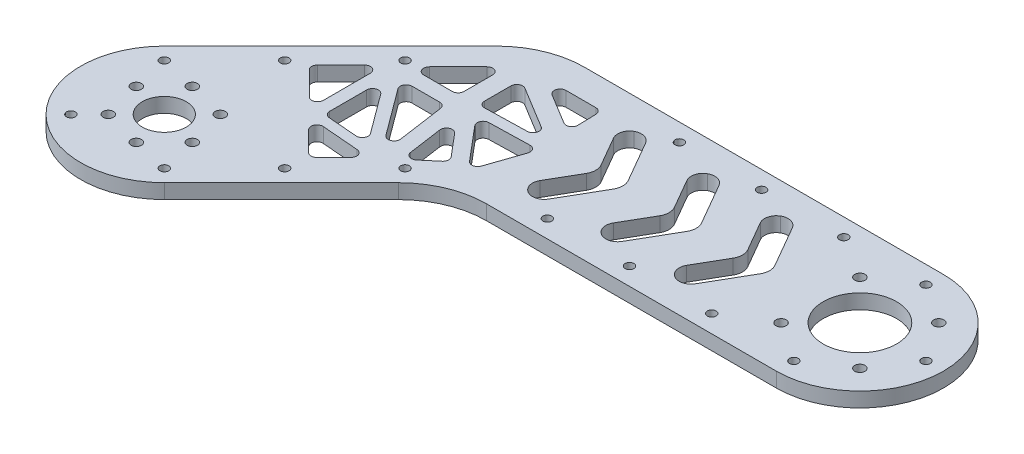
SolidWorks part; units mm, degrees
ref_plane "前视基准面" through (0, 0, 0) normal (0, 0, 1) x (1, 0, 0)
ref_plane "上视基准面" through (0, 0, 0) normal (0, 1, 0) x (1, 0, 0)
ref_plane "右视基准面" through (0, 0, 0) normal (1, 0, 0) x (0, 0, -1)
sketch "草图1" plane through (0, 0, 0) normal (0, 1, 0) x (1, 0, 0)
  line L0 (-20.1525, 20.1525) -> (45.1949, 85.5)
  line L1 (20.1525, -20.1525) -> (68.8051, 28.5)
  line L2 (68.8051, 28.5) -> (180, 28.5)
  line L3 (45.1949, 85.5) -> (180, 85.5)
  line L4 (20.1525, -20.1525) -> (137.6118, -20.1525) construction
  circle A0 centre (0, 0) radius 28.5
  circle A1 centre (180, 57) radius 28.5
  dimension "D1" = 57
  dimension "D3" = 57
  dimension "D2" = 57
  dimension "D4" = 57
  dimension "D5" = 45
  dimension "D6" = 180
extrude "凸台-拉伸1" add sketch "草图1" along normal blind 5 contours A1 L3 L0 A0 L1 L2 | A0 | A1 region at (80.8159, 0, -50.6724) region at (0, 0, 0) region at (180, 0, -57)
fillet "圆角1" radius 30 1 edges at (68.8051, 2.5, -28.5)
fillet "圆角2" radius 30 1 edges at (45.1949, 2.5, -85.5)
sketch "草图2" plane through (0, 5, 0) normal (0, 1, 0) x (1, 0, 0)
  line L0 (180, 57) -> (-10.2315, 57) construction
  line L1 (150, 57) -> (138.453, 77)
  line L2 (138.453, 77) -> (131.5248, 73)
  line L3 (131.5248, 73) -> (140.7624, 57)
  line L4 (131.5248, 41) -> (140.7624, 57)
  line L5 (150, 57) -> (138.453, 37)
  line L6 (138.453, 37) -> (131.5248, 41)
  line L7 (106.5248, 41) -> (115.7624, 57)
  line L8 (106.5248, 73) -> (115.7624, 57)
  line L9 (113.453, 77) -> (106.5248, 73)
  line L10 (125, 57) -> (113.453, 77)
  line L11 (125, 57) -> (113.453, 37)
  line L12 (113.453, 37) -> (106.5248, 41)
  line L13 (81.5248, 41) -> (90.7624, 57)
  line L14 (81.5248, 73) -> (90.7624, 57)
  line L15 (88.453, 77) -> (81.5248, 73)
  line L16 (100, 57) -> (88.453, 77)
  line L17 (100, 57) -> (88.453, 37)
  line L18 (88.453, 37) -> (81.5248, 41)
  dimension "D1" = 8
  dimension "D2" = 20
  dimension "D3" = 30
  dimension "D4" = 60
  dimension "D5" = 3
extrude "切除-拉伸1" cut sketch "草图2" against normal blind 5
fillet "圆角3" radius 5 6 edges at (140.7624, 2.5, -57) (115.7624, 2.5, -57) (90.7624, 2.5, -57) (100, 2.5, -57) (125, 2.5, -57) (150, 2.5, -57)
fillet "圆角4" radius 4 12 edges at (88.453, 2.5, -37) (81.5248, 2.5, -41) (81.5248, 2.5, -73) (106.5248, 2.5, -73) (88.453, 2.5, -77) (113.453, 2.5, -77) (113.453, 2.5, -37) (106.5248, 2.5, -41) (131.5248, 2.5, -41) (138.453, 2.5, -37) (131.5248, 2.5, -73) (138.453, 2.5, -77)
sketch "草图3" plane through (0, 0, 0) normal (0, -1, 0) x (1, 0, 0)
  line L0 (180, -57) -> (216.2615, -57) construction
  line L1 (180, -57) -> (193.435, -43.565) construction
  circle A0 centre (180, -57) radius 19 construction
  circle A7 centre (193.435, -43.565) radius 1.75
  circle A8 centre (193.435, -70.435) radius 1.75
  circle A9 centre (166.565, -70.435) radius 1.75
  circle A10 centre (166.565, -43.565) radius 1.75
  point P15 (180, -57)
  point P18 (180, -57)
  dimension "D1" = 38
  dimension "D2" = 45
  dimension "D3" = 3.5
  dimension "D4" = 4
extrude "切除-拉伸2" cut sketch "草图3" against normal blind 5
sketch "草图4" plane through (0, 0, 0) normal (0, -1, 0) x (1, 0, 0)
  line L0 (0, 0) -> (-20.1525, 20.1525) construction
  circle A0 centre (0, 0) radius 13.5 construction
  circle A1 centre (3.4941, 13.04) radius 1.75
  circle A2 centre (-9.5459, 9.5459) radius 1.75
  circle A3 centre (13.04, 3.4941) radius 1.75
  circle A4 centre (9.5459, -9.5459) radius 1.75
  circle A5 centre (-3.4941, -13.04) radius 1.75
  circle A6 centre (-13.04, -3.4941) radius 1.75
  point P20 (0, 0)
  dimension "D1" = 27
  dimension "D2" = 3.5
  dimension "D3" = 6
extrude "切除-拉伸3" cut sketch "草图4" against normal blind 5
sketch "草图5" plane through (0, 5, 0) normal (0, 1, 0) x (1, 0, 0)
  line L0 (0, 0) -> (65.1893, 65.1893) construction
  line L1 (-20.1525, 20.1525) -> (36.4081, 76.7132) construction
  line L2 (47.7297, 30.052) -> (30.052, 47.7297)
  line L3 (30.052, 47.7297) -> (28.2843, 28.2843)
  line L4 (24.7487, 50.2046) -> (12.0208, 37.4767)
  line L5 (12.0208, 37.4767) -> (22.6274, 26.8701)
  line L6 (22.6274, 26.8701) -> (24.7487, 50.2046)
  line L7 (47.7297, 30.052) -> (28.2843, 28.2843)
  line L8 (37.4767, 12.0208) -> (26.8701, 22.6274)
  line L9 (50.2046, 24.7487) -> (37.4767, 12.0208)
  line L10 (26.8701, 22.6274) -> (50.2046, 24.7487)
  point P12 (38.8909, 38.8909)
  dimension "D1" = 15
  dimension "D2" = 18
  dimension "D3" = 25
  dimension "D4" = 3
  dimension "D5" = 35
  dimension "D6" = 20
sketch "草图7" plane through (0, 5, 0) normal (0, 1, 0) x (1, 0, 0)
  line L0 (180, 57) -> (5.0176, 57) construction
  line L4 (37.3024, 11.8794) -> (47.5413, 22.1184)
  line L8 (89.9889, 57) -> (89.9889, 67.6591) construction
  line L9 (73.4605, 75.5061) -> (73.7578, 63.626)
  line L10 (73.7578, 63.626) -> (54.2263, 75.5061)
  line L11 (54.2263, 75.5061) -> (73.4605, 75.5061)
  line L12 (44.295, 72.4023) -> (27.7117, 55.819)
  line L13 (27.7117, 55.819) -> (44.295, 55.819)
  line L14 (44.295, 55.819) -> (44.295, 72.4023)
  line L15 (50.6369, 71.0152) -> (50.6369, 56.4235)
  line L16 (50.6369, 56.4235) -> (73.6786, 57)
  line L17 (73.6786, 57) -> (50.6369, 71.0152)
  line L18 (53.5277, 52.7613) -> (74.2599, 53.28)
  line L19 (74.2599, 53.28) -> (68.128, 35.4384)
  line L20 (68.128, 35.4384) -> (53.5277, 52.7613)
  line L21 (53.6788, 27.1882) -> (62.7017, 34.7929)
  line L22 (62.7017, 34.7929) -> (50.531, 49.2331)
  line L23 (50.531, 49.2331) -> (53.6788, 27.1882)
  line L24 (45.0473, 50.5224) -> (29.9222, 50.5224)
  line L25 (29.9222, 50.5224) -> (48.6672, 25.1716)
  line L26 (48.6672, 25.1716) -> (45.0473, 50.5224)
  line L27 (22.9587, 52.0768) -> (10.1382, 39.2563)
  line L28 (10.1382, 39.2563) -> (22.9587, 26.4359)
  line L29 (22.9587, 26.4359) -> (22.9587, 52.0768)
  line L30 (27.2619, 47.7479) -> (43.3792, 25.9508)
  line L31 (43.3792, 25.9508) -> (27.2619, 27.2619)
  line L32 (0, 0) -> (65.1893, 65.1893) construction
  line L33 (27.2619, 27.2619) -> (27.2619, 47.7479)
  line L34 (47.5413, 22.1184) -> (25.2502, 23.9316)
  line L35 (25.2502, 23.9316) -> (37.3024, 11.8794)
  line L36 (57.6213, 85.5) -> (180, 85.5) construction
  line L37 (-20.1525, 20.1525) -> (36.4081, 76.7132) construction
  line L38 (20.1525, -20.1525) -> (60.0183, 19.7132) construction
  arc A0 (89.319, 54.5) -> (89.319, 59.5) centre (84.9889, 57) ccw construction
extrude "切除-拉伸6" cut sketch "草图7" against normal blind 10
fillet "圆角7" radius 2 18 edges at (29.9222, 2.5, -50.5224) (48.6672, 2.5, -25.1716) (45.0473, 2.5, -50.5224) (53.6788, 2.5, -27.1882) (62.7017, 2.5, -34.7929) (50.531, 2.5, -49.2331) (68.128, 2.5, -35.4384) (53.5277, 2.5, -52.7613) (74.2599, 2.5, -53.28) (73.7578, 2.5, -63.626) (54.2263, 2.5, -75.5061) (73.4605, 2.5, -75.5061) (50.6369, 2.5, -56.4235) (73.6786, 2.5, -57) (50.6369, 2.5, -71.0152) (44.295, 2.5, -55.819) (27.7117, 2.5, -55.819) (44.295, 2.5, -72.4023)
fillet "圆角8" radius 2 9 edges at (37.3024, 2.5, -11.8794) (25.2502, 2.5, -23.9316) (47.5413, 2.5, -22.1184) (43.3792, 2.5, -25.9508) (27.2619, 2.5, -27.2619) (27.2619, 2.5, -47.7479) (22.9587, 2.5, -26.4359) (10.1382, 2.5, -39.2563) (22.9587, 2.5, -52.0768)
sketch "草图8" plane through (0, 5, 0) normal (0, 1, 0) x (1, 0, 0)
  line L0 (0, 0) -> (-15.9099, -15.9099) construction
  line L1 (-20.1525, 20.1525) -> (20.1525, -20.1525) construction
  line L2 (-15.9099, 15.9099) -> (45.5568, 77.3766) construction
  line L3 (-20.1525, 20.1525) -> (36.4081, 76.7132) construction
  line L4 (15.9099, -15.9099) -> (54.5464, 22.7266) construction
  line L5 (20.1525, -20.1525) -> (60.0183, 19.7132) construction
  line L6 (180, 79.5) -> (59.1595, 79.5) construction
  line L7 (180, 34.5) -> (75.7291, 34.5) construction
  circle A0 centre (0, 0) radius 22.5 construction
  circle A1 centre (-15.9099, -15.9099) radius 1.5
  circle A2 centre (-15.9099, 15.9099) radius 1.5
  circle A3 centre (15.9099, -15.9099) radius 1.5
  circle A4 centre (4.5962, 36.416) radius 1.5
  circle A5 centre (25.1023, 56.9221) radius 1.5
  circle A7 centre (36.416, 4.5962) radius 1.5
  circle A8 centre (56.9221, 25.1023) radius 1.5
  circle A9 centre (180, 57) radius 22.5 construction
  circle A10 centre (180, 79.5) radius 1.5
  circle A11 centre (180, 34.5) radius 1.5
  circle A12 centre (152, 79.5) radius 1.5
  circle A13 centre (124, 79.5) radius 1.5
  circle A14 centre (96, 79.5) radius 1.5
  circle A16 centre (152, 34.5) radius 1.5
  circle A17 centre (124, 34.5) radius 1.5
  circle A18 centre (96, 34.5) radius 1.5
  circle A19 centre (202.5, 57) radius 1.5
  dimension "D1" = 45
  dimension "D2" = 3
  dimension "D3" = 3
  dimension "D4" = 3
  dimension "D7" = 45
  dimension "D8" = 3
  dimension "D9" = 3
  dimension "D12" = 3
  dimension "D5" = 3
  dimension "D6" = 3
  dimension "D10" = 4
  dimension "D11" = 4
extrude "切除-拉伸7" cut sketch "草图8" against normal blind 10
sketch "草图9" plane through (0, 5, 0) normal (0, 1, 0) x (1, 0, 0)
  line L0 (46.1408, 83.2164) -> (69.751, 26.2164) construction
  arc A0 (57.6213, 85.5) -> (36.4081, 76.7132) centre (57.6213, 55.5) ccw construction
  arc A1 (81.2315, 28.5) -> (60.0183, 19.7132) centre (81.2315, -1.5) ccw construction
sketch "草图10" plane through (0, 5, 0) normal (0, 1, 0) x (1, 0, 0)
  circle A0 centre (0, 0) radius 7.5
  circle A1 centre (180, 57) radius 12.5
  dimension "D1" = 15
  dimension "D2" = 25
extrude "切除-拉伸8" cut sketch "草图10" against normal blind 10
